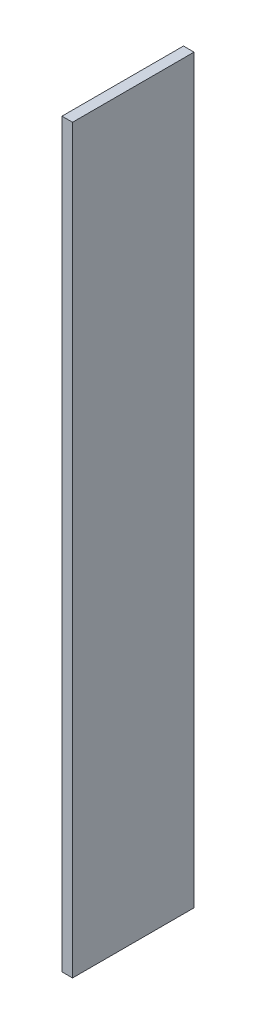
SolidWorks part; units mm, degrees
material "6061-T6 (SS)"
ref_plane "Front" through (0, 0, 0) normal (0, 0, 1) x (1, 0, 0)
ref_plane "Top" through (0, 0, 0) normal (0, 1, 0) x (1, 0, 0)
ref_plane "Right" through (0, 0, 0) normal (1, 0, 0) x (0, 0, -1)
sketch "Sketch1" plane through (0, 0, 0) normal (0, 1, 0) x (1, 0, 0)
  line L1 (-50.8, 584.2) -> (50.8, 584.2)
  line L2 (-50.8, 584.2) -> (-50.8, -584.2)
  line L3 (-50.8, -584.2) -> (50.8, -584.2)
  line L4 (50.8, 584.2) -> (50.8, -584.2)
  line L5 (-50.8, 584.2) -> (50.8, -584.2) construction
  line L6 (-50.8, -584.2) -> (50.8, 584.2) construction
  point P0 (0, 0)
  dimension "D1" = 1168.4
  dimension "D2" = 101.6
extrude "Boss-Extrude1" add sketch "Sketch1" along normal blind 7124.7
sketch "Sketch2" plane through (50.8, 0, 0) normal (1, 0, 0) x (0, 0, -1)
  line L0 (584.2, 7124.7) -> (584.2, 0) construction
  line L1 (584.2, 0) -> (431.8, 0)
  line L2 (584.2, 0) -> (584.2, 2286)
  line L3 (584.2, 2286) -> (431.8, 2286)
  line L4 (431.8, 0) -> (431.8, 2286)
  line L6 (-584.2, 0) -> (584.2, 0) construction
  dimension "D1" = 152.4
  dimension "D2" = 2286
extrude "Cut-Extrude1" [suppressed] cut sketch "Sketch2" against normal through all
sketch "Sketch3" [suppressed] plane through (50.8, 0, 0) normal (1, 0, 0) x (0, 0, -1)
  line L0 (-584.2, 7124.7) -> (-584.2, 0) construction
  line L2 (-584.2, 2286) -> (-584.2, 0)
  line L3 (-584.2, 0) -> (584.2, 0)
  line L4 (-381, 0) -> (584.2, 0)
  line L5 (-381, 4267.2) -> (-381, 0)
  line L6 (584.2, 4267.2) -> (-381, 4267.2)
  line L7 (584.2, 0) -> (584.2, 4267.2)
  line L8 (-381, 0) -> (584.2, 0) construction
  line L9 (-381, 4267.2) -> (-381, 0) construction
  line L12 (584.2, 2286) -> (584.2, 0)
  line L13 (-584.2, 2286) -> (584.2, 2286)
  dimension "D2" = 2286
  dimension "D1" = 0
extrude "Cut-Extrude2" [suppressed] cut sketch "Sketch3" against normal through all
sketch "Sketch4" [suppressed] plane through (-76.2, 0, 0) normal (-1, 0, 0) x (0, 0, 1)
  line L0 (-584.2, 6400.8) -> (584.2, 6400.8) construction
  line L1 (584.2, 6400.8) -> (584.2, 0) construction
  circle A0 centre (177.8, 5994.4) radius 152.4
  dimension "D1" = 304.8
  dimension "D2" = 406.4
  dimension "D3" = 406.4
extrude "Cut-Extrude3" [suppressed] cut sketch "Sketch4" against normal through all and the other way through all
sketch "Sketch5" [suppressed] plane through (-76.2, 0, 0) normal (-1, 0, 0) x (0, 0, 1)
  line L0 (584.2, 6400.8) -> (584.2, 0) construction
  line L1 (-584.2, 0) -> (584.2, 0) construction
  circle A0 centre (177.8, 406.4) radius 152.4
  dimension "D1" = 304.8
  dimension "D2" = 406.4
  dimension "D3" = 406.4
extrude "Cut-Extrude4" [suppressed] cut sketch "Sketch5" against normal through all
sketch "Sketch6" [suppressed] plane through (50.8, 0, 0) normal (1, 0, 0) x (0, 0, -1)
  line L1 (584.2, 0) -> (-330.2, 0)
  line L2 (584.2, 0) -> (584.2, 4267.2)
  line L3 (584.2, 4267.2) -> (-330.2, 4267.2)
  line L4 (-330.2, 0) -> (-330.2, 4267.2)
  dimension "D1" = 4267.2
  dimension "D2" = 914.4
extrude "Cut-Extrude5" [suppressed] cut sketch "Sketch6" against normal through all
sketch "Sketch7" [suppressed] plane through (50.8, 0, 0) normal (1, 0, 0) x (0, 0, -1)
  line L1 (-584.2, 0) -> (330.2, 0)
  line L2 (-584.2, 0) -> (-584.2, 4267.2)
  line L3 (-584.2, 4267.2) -> (330.2, 4267.2)
  line L4 (330.2, 0) -> (330.2, 4267.2)
  dimension "D1" = 4267.2
  dimension "D2" = 914.4
extrude "Cut-Extrude6" [suppressed] cut sketch "Sketch7" against normal through all
